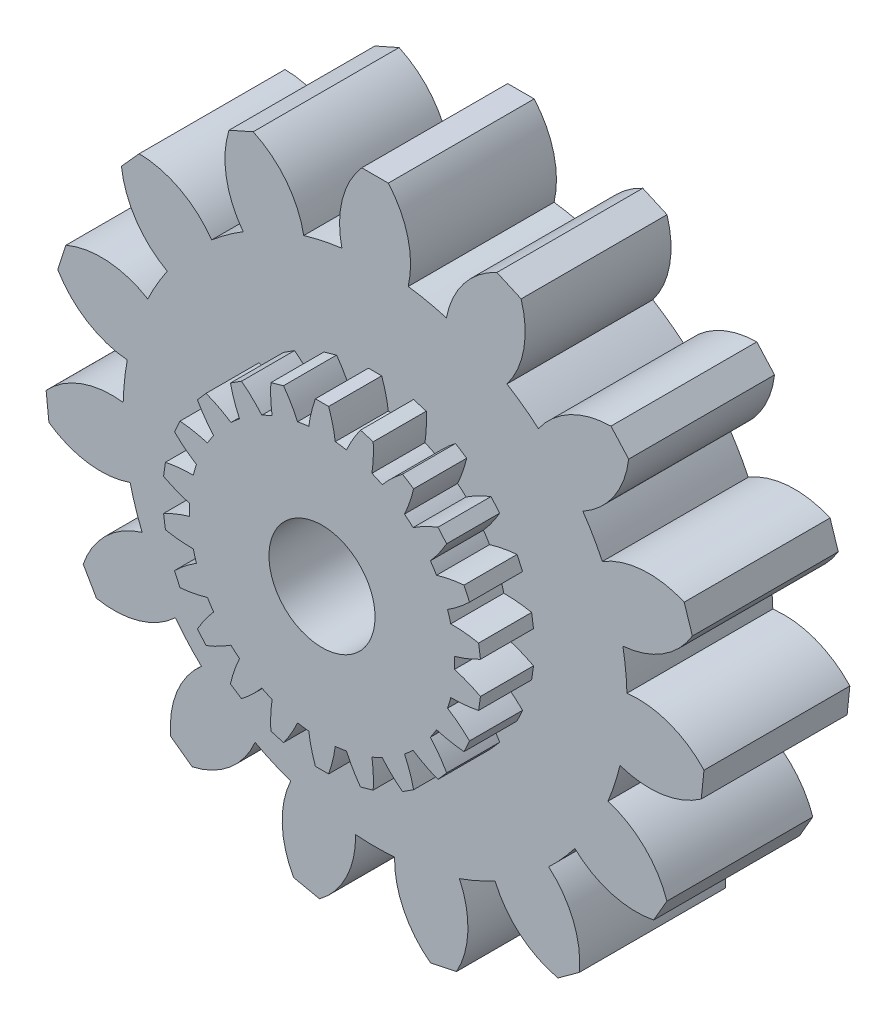
SolidWorks part; units mm, degrees
ref_plane "前视基准面" through (0, 0, 0) normal (0, 0, 1) x (1, 0, 0)
ref_plane "上视基准面" through (0, 0, 0) normal (0, 1, 0) x (1, 0, 0)
ref_plane "右视基准面" through (0, 0, 0) normal (1, 0, 0) x (0, 0, -1)
sketch "草图2" plane through (0, 0, 0) normal (0, 0, 1) x (1, 0, 0)
  circle A0 centre (0, 0) radius 9.5
extrude "凸台-拉伸1" add sketch "草图2" along normal blind 5.5
sketch "草图3" plane through (0, 0, 5.5) normal (0, 0, 1) x (1, 0, 0)
  line L0 (5.5074, 11.1405) -> (4.5938, 11.5472)
  line L1 (0.5, 12.4174) -> (-0.5, 12.4174)
  line L2 (9.5625, 7.9373) -> (8.8934, 8.6804)
  line L3 (11.9642, 3.3617) -> (11.6551, 4.3127)
  line L4 (12.2971, -1.7952) -> (12.4016, -0.8007)
  line L5 (10.5038, -6.6417) -> (11.0038, -5.7757)
  line L6 (6.8943, -10.3398) -> (7.7033, -9.752)
  line L7 (2.0926, -12.25) -> (3.0708, -12.0421)
  line L8 (-3.0708, -12.0421) -> (-2.0926, -12.25)
  line L9 (-7.7033, -9.752) -> (-6.8943, -10.3398)
  line L10 (-11.0038, -5.7757) -> (-10.5038, -6.6417)
  line L11 (-12.4016, -0.8007) -> (-12.2971, -1.7952)
  line L12 (-11.6551, 4.3127) -> (-11.9642, 3.3617)
  line L13 (-8.8934, 8.6804) -> (-9.5625, 7.9373)
  line L14 (-4.5938, 11.5472) -> (-5.5074, 11.1405)
  arc A0 (1.25, 9.4174) -> (-1.25, 9.4174) centre (0, 0) ccw
  arc A1 (-0.5, 12.4174) -> (-1.25, 9.4174) centre (2.0424, 10.1881) ccw
  arc A2 (0.5, 12.4174) -> (1.25, 9.4174) centre (-2.0424, 10.1881) cw
  arc A3 (4.9723, 8.0948) -> (2.6885, 9.1116) centre (0, 0) ccw
  arc A4 (4.5938, 11.5472) -> (2.6885, 9.1116) centre (6.0097, 8.4765) ccw
  arc A5 (5.5074, 11.1405) -> (4.9723, 8.0948) centre (2.278, 10.138) cw
  arc A6 (7.8349, 5.3725) -> (6.1621, 7.2304) centre (0, 0) ccw
  arc A7 (8.8934, 8.6804) -> (6.1621, 7.2304) centre (8.9378, 5.2993) ccw
  arc A8 (9.5625, 7.9373) -> (7.8349, 5.3725) centre (6.2046, 8.3349) cw
  arc A9 (9.3428, 1.7213) -> (8.5702, 4.099) centre (0, 0) ccw
  arc A10 (11.6551, 4.3127) -> (8.5702, 4.099) centre (10.3206, 1.2058) ccw
  arc A11 (11.9642, 3.3617) -> (9.3428, 1.7213) centre (9.0583, 5.0907) cw
  arc A12 (9.2352, -2.2275) -> (9.4965, 0.2588) centre (0, 0) ccw
  arc A13 (12.4016, -0.8007) -> (9.4965, 0.2588) centre (9.9188, -3.0962) ccw
  arc A14 (12.2971, -1.7952) -> (9.2352, -2.2275) centre (10.3457, 0.9663) cw
  arc A15 (7.5307, -5.7912) -> (8.7807, -3.6262) centre (0, 0) ccw
  arc A16 (11.0038, -5.7757) -> (8.7807, -3.6262) centre (7.8019, -6.8628) ccw
  arc A17 (10.5038, -6.6417) -> (7.5307, -5.7912) centre (9.8443, -3.3253) cw
  arc A18 (4.5241, -8.3536) -> (6.5467, -6.8841) centre (0, 0) ccw
  arc A19 (7.7033, -9.752) -> (6.5467, -6.8841) centre (4.336, -9.4428) ccw
  arc A20 (6.8943, -10.3398) -> (4.5241, -8.3536) centre (7.6407, -7.0418) cw
  arc A21 (0.7353, -9.4715) -> (3.1807, -8.9517) centre (0, 0) ccw
  arc A22 (3.0708, -12.0421) -> (3.1807, -8.9517) centre (0.1204, -10.3901) ccw
  arc A23 (2.0926, -12.25) -> (0.7353, -9.4715) centre (4.116, -9.5408) cw
  arc A24 (-3.1807, -8.9517) -> (-0.7353, -9.4715) centre (0, 0) ccw
  arc A25 (-2.0926, -12.25) -> (-0.7353, -9.4715) centre (-4.116, -9.5408) ccw
  arc A26 (-3.0708, -12.0421) -> (-3.1807, -8.9517) centre (-0.1204, -10.3901) cw
  arc A27 (-6.5467, -6.8841) -> (-4.5241, -8.3536) centre (0, 0) ccw
  arc A28 (-6.8943, -10.3398) -> (-4.5241, -8.3536) centre (-7.6407, -7.0418) ccw
  arc A29 (-7.7033, -9.752) -> (-6.5467, -6.8841) centre (-4.336, -9.4428) cw
  arc A30 (-8.7807, -3.6262) -> (-7.5307, -5.7912) centre (0, 0) ccw
  arc A31 (-10.5038, -6.6417) -> (-7.5307, -5.7912) centre (-9.8443, -3.3253) ccw
  arc A32 (-11.0038, -5.7757) -> (-8.7807, -3.6262) centre (-7.8019, -6.8628) cw
  arc A33 (-9.4965, 0.2588) -> (-9.2352, -2.2275) centre (0, 0) ccw
  arc A34 (-12.2971, -1.7952) -> (-9.2352, -2.2275) centre (-10.3457, 0.9663) ccw
  arc A35 (-12.4016, -0.8007) -> (-9.4965, 0.2588) centre (-9.9188, -3.0962) cw
  arc A36 (-8.5702, 4.099) -> (-9.3428, 1.7213) centre (0, 0) ccw
  arc A37 (-11.9642, 3.3617) -> (-9.3428, 1.7213) centre (-9.0583, 5.0907) ccw
  arc A38 (-11.6551, 4.3127) -> (-8.5702, 4.099) centre (-10.3206, 1.2058) cw
  arc A39 (-6.1621, 7.2304) -> (-7.8349, 5.3725) centre (0, 0) ccw
  arc A40 (-9.5625, 7.9373) -> (-7.8349, 5.3725) centre (-6.2046, 8.3349) ccw
  arc A41 (-8.8934, 8.6804) -> (-6.1621, 7.2304) centre (-8.9378, 5.2993) cw
  arc A42 (-2.6885, 9.1116) -> (-4.9723, 8.0948) centre (0, 0) ccw
  arc A43 (-5.5074, 11.1405) -> (-4.9723, 8.0948) centre (-2.278, 10.138) ccw
  arc A44 (-4.5938, 11.5472) -> (-2.6885, 9.1116) centre (-6.0097, 8.4765) cw
  dimension "D1" = 15
extrude "凸台-拉伸2" add sketch "草图3" against normal up to surface (5.5 mm away) up to face at (9.5, 0, 0)
sketch "草图4" plane through (0, 0, 5.5) normal (0, 0, 1) x (1, 0, 0)
  circle A0 centre (0, 0) radius 5
extrude "凸台-拉伸3" add sketch "草图4" along normal blind 2
sketch "草图5" plane through (0, 0, 7.5) normal (0, 0, 1) x (1, 0, 0)
  line L0 (1.9303, 5.6865) -> (1.4505, 5.8274)
  line L1 (3.4542, 4.9124) -> (3.0335, 5.1827)
  line L2 (0.25, 6) -> (-0.25, 6)
  line L3 (4.6982, 3.7402) -> (4.3708, 4.1181)
  line L4 (5.5616, 2.2651) -> (5.3539, 2.7199)
  line L5 (5.9745, 0.6064) -> (5.9033, 1.1013)
  line L6 (5.9033, -1.1013) -> (5.9745, -0.6064)
  line L7 (5.3539, -2.7199) -> (5.5616, -2.2651)
  line L8 (4.3708, -4.1181) -> (4.6982, -3.7402)
  line L9 (3.0335, -5.1827) -> (3.4542, -4.9124)
  line L10 (1.4505, -5.8274) -> (1.9303, -5.6865)
  line L11 (-0.25, -6) -> (0.25, -6)
  line L12 (-1.9303, -5.6865) -> (-1.4505, -5.8274)
  line L13 (-3.4542, -4.9124) -> (-3.0335, -5.1827)
  line L14 (-4.6982, -3.7402) -> (-4.3708, -4.1181)
  line L15 (-5.5616, -2.2651) -> (-5.3539, -2.7199)
  line L16 (-5.9745, -0.6064) -> (-5.9033, -1.1013)
  line L17 (-5.9033, 1.1013) -> (-5.9745, 0.6064)
  line L18 (-5.3539, 2.7199) -> (-5.5616, 2.2651)
  line L19 (-4.3708, 4.1181) -> (-4.6982, 3.7402)
  line L20 (-3.0335, 5.1827) -> (-3.4542, 4.9124)
  line L21 (-1.4505, 5.8274) -> (-1.9303, 5.6865)
  arc A0 (0.5, 4.9749) -> (-0.5, 4.9749) centre (0, 0) ccw
  arc A1 (-0.25, 6) -> (-0.5, 4.9749) centre (4.571, 4.2812) ccw
  arc A2 (0.25, 6) -> (0.5, 4.9749) centre (-4.571, 4.2812) cw
  arc A3 (1.8813, 4.6326) -> (0.9219, 4.9143) centre (0, 0) ccw
  arc A4 (1.4505, 5.8274) -> (0.9219, 4.9143) centre (5.592, 2.82) ccw
  arc A5 (1.9303, 5.6865) -> (1.8813, 4.6326) centre (-3.1797, 5.3956) cw
  arc A6 (3.1103, 3.9149) -> (2.269, 4.4555) centre (0, 0) ccw
  arc A7 (3.0335, 5.1827) -> (2.269, 4.4555) centre (6.1599, 1.1303) ccw
  arc A8 (3.4542, 4.9124) -> (3.1103, 3.9149) centre (-1.5308, 6.0728) cw
  arc A9 (4.0872, 2.88) -> (3.4324, 3.6358) centre (0, 0) ccw
  arc A10 (4.3708, 4.1181) -> (3.4324, 3.6358) centre (6.2289, -0.6509) ccw
  arc A11 (4.6982, 3.7402) -> (4.0872, 2.88) centre (0.2422, 6.2581) cw
  arc A12 (4.7331, 1.6118) -> (4.3177, 2.5215) centre (0, 0) ccw
  arc A13 (5.3539, 2.7199) -> (4.3177, 2.5215) centre (5.7932, -2.3794) ccw
  arc A14 (5.5616, 2.2651) -> (4.7331, 1.6118) centre (1.9955, 5.9364) cw
  arc A15 (4.9955, 0.2131) -> (4.8531, 1.2029) centre (0, 0) ccw
  arc A16 (5.9033, 1.1013) -> (4.8531, 1.2029) centre (4.8881, -3.9152) ccw
  arc A17 (5.9745, 0.6064) -> (4.9955, 0.2131) centre (3.5871, 5.1337) cw
  arc A18 (4.8531, -1.2029) -> (4.9955, -0.2131) centre (0, 0) ccw
  arc A19 (5.9745, -0.6064) -> (4.9955, -0.2131) centre (3.5871, -5.1337) ccw
  arc A20 (5.9033, -1.1013) -> (4.8531, -1.2029) centre (4.8881, 3.9152) cw
  arc A21 (4.3177, -2.5215) -> (4.7331, -1.6118) centre (0, 0) ccw
  arc A22 (5.5616, -2.2651) -> (4.7331, -1.6118) centre (1.9955, -5.9364) ccw
  arc A23 (5.3539, -2.7199) -> (4.3177, -2.5215) centre (5.7932, 2.3794) cw
  arc A24 (3.4324, -3.6358) -> (4.0872, -2.88) centre (0, 0) ccw
  arc A25 (4.6982, -3.7402) -> (4.0872, -2.88) centre (0.2422, -6.2581) ccw
  arc A26 (4.3708, -4.1181) -> (3.4324, -3.6358) centre (6.2289, 0.6509) cw
  arc A27 (2.269, -4.4555) -> (3.1103, -3.9149) centre (0, 0) ccw
  arc A28 (3.4542, -4.9124) -> (3.1103, -3.9149) centre (-1.5308, -6.0728) ccw
  arc A29 (3.0335, -5.1827) -> (2.269, -4.4555) centre (6.1599, -1.1303) cw
  arc A30 (0.9219, -4.9143) -> (1.8813, -4.6326) centre (0, 0) ccw
  arc A31 (1.9303, -5.6865) -> (1.8813, -4.6326) centre (-3.1797, -5.3956) ccw
  arc A32 (1.4505, -5.8274) -> (0.9219, -4.9143) centre (5.592, -2.82) cw
  arc A33 (-0.5, -4.9749) -> (0.5, -4.9749) centre (0, 0) ccw
  arc A34 (0.25, -6) -> (0.5, -4.9749) centre (-4.571, -4.2812) ccw
  arc A35 (-0.25, -6) -> (-0.5, -4.9749) centre (4.571, -4.2812) cw
  arc A36 (-1.8813, -4.6326) -> (-0.9219, -4.9143) centre (0, 0) ccw
  arc A37 (-1.4505, -5.8274) -> (-0.9219, -4.9143) centre (-5.592, -2.82) ccw
  arc A38 (-1.9303, -5.6865) -> (-1.8813, -4.6326) centre (3.1797, -5.3956) cw
  arc A39 (-3.1103, -3.9149) -> (-2.269, -4.4555) centre (0, 0) ccw
  arc A40 (-3.0335, -5.1827) -> (-2.269, -4.4555) centre (-6.1599, -1.1303) ccw
  arc A41 (-3.4542, -4.9124) -> (-3.1103, -3.9149) centre (1.5308, -6.0728) cw
  arc A42 (-4.0872, -2.88) -> (-3.4324, -3.6358) centre (0, 0) ccw
  arc A43 (-4.3708, -4.1181) -> (-3.4324, -3.6358) centre (-6.2289, 0.6509) ccw
  arc A44 (-4.6982, -3.7402) -> (-4.0872, -2.88) centre (-0.2422, -6.2581) cw
  arc A45 (-4.7331, -1.6118) -> (-4.3177, -2.5215) centre (0, 0) ccw
  arc A46 (-5.3539, -2.7199) -> (-4.3177, -2.5215) centre (-5.7932, 2.3794) ccw
  arc A47 (-5.5616, -2.2651) -> (-4.7331, -1.6118) centre (-1.9955, -5.9364) cw
  arc A48 (-4.9955, -0.2131) -> (-4.8531, -1.2029) centre (0, 0) ccw
  arc A49 (-5.9033, -1.1013) -> (-4.8531, -1.2029) centre (-4.8881, 3.9152) ccw
  arc A50 (-5.9745, -0.6064) -> (-4.9955, -0.2131) centre (-3.5871, -5.1337) cw
  arc A51 (-4.8531, 1.2029) -> (-4.9955, 0.2131) centre (0, 0) ccw
  arc A52 (-5.9745, 0.6064) -> (-4.9955, 0.2131) centre (-3.5871, 5.1337) ccw
  arc A53 (-5.9033, 1.1013) -> (-4.8531, 1.2029) centre (-4.8881, -3.9152) cw
  arc A54 (-4.3177, 2.5215) -> (-4.7331, 1.6118) centre (0, 0) ccw
  arc A55 (-5.5616, 2.2651) -> (-4.7331, 1.6118) centre (-1.9955, 5.9364) ccw
  arc A56 (-5.3539, 2.7199) -> (-4.3177, 2.5215) centre (-5.7932, -2.3794) cw
  arc A57 (-3.4324, 3.6358) -> (-4.0872, 2.88) centre (0, 0) ccw
  arc A58 (-4.6982, 3.7402) -> (-4.0872, 2.88) centre (-0.2422, 6.2581) ccw
  arc A59 (-4.3708, 4.1181) -> (-3.4324, 3.6358) centre (-6.2289, -0.6509) cw
  arc A60 (-2.269, 4.4555) -> (-3.1103, 3.9149) centre (0, 0) ccw
  arc A61 (-3.4542, 4.9124) -> (-3.1103, 3.9149) centre (1.5308, 6.0728) ccw
  arc A62 (-3.0335, 5.1827) -> (-2.269, 4.4555) centre (-6.1599, 1.1303) cw
  arc A63 (-0.9219, 4.9143) -> (-1.8813, 4.6326) centre (0, 0) ccw
  arc A64 (-1.9303, 5.6865) -> (-1.8813, 4.6326) centre (3.1797, 5.3956) ccw
  arc A65 (-1.4505, 5.8274) -> (-0.9219, 4.9143) centre (-5.592, 2.82) cw
  dimension "D1" = 22
extrude "凸台-拉伸4" add sketch "草图5" against normal up to next
sketch "草图6" plane through (0, 0, 7.5) normal (0, 0, 1) x (1, 0, 0)
  circle A0 centre (0, 0) radius 2
extrude "切除-拉伸1" cut sketch "草图6" against normal through all
extrude "切除-拉伸2" cut sketch "草图5<2>" along normal blind 2 from offset 7.5 offset against normal yes
sketch "草图5<2>" plane through (0, 0, 7.5) normal (0, 0, 1) x (1, 0, 0) same geometry as "草图5"
sketch "草图8" plane through (0, 0, 0) normal (0, 0, -1) x (-1, 0, 0)
  circle A0 centre (0, 0) radius 5
extrude "切除-拉伸3" cut sketch "草图8" against normal blind 2
